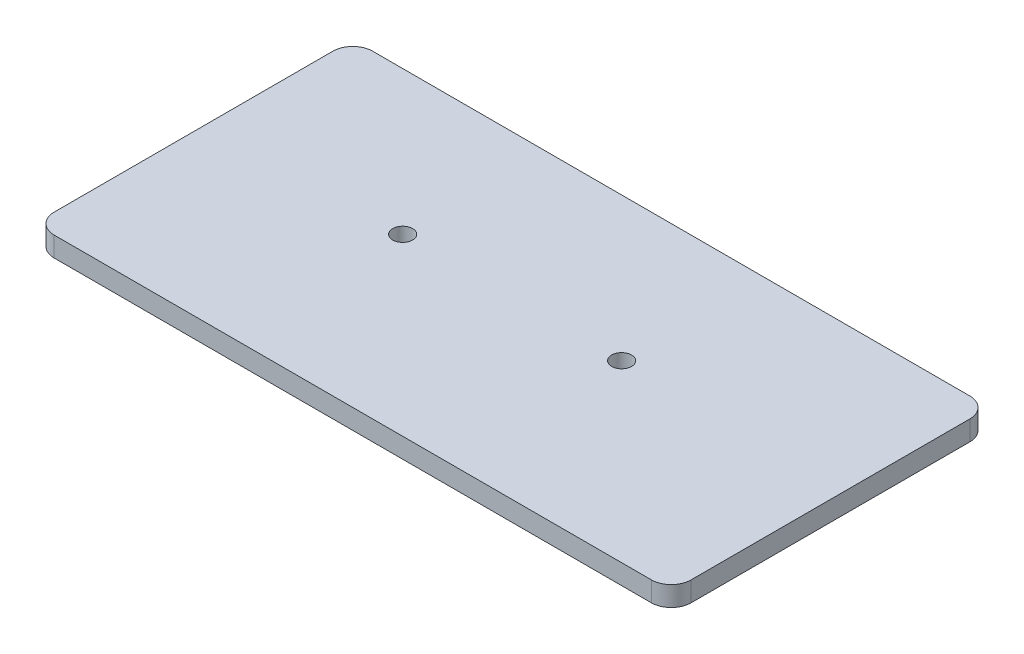
SolidWorks part; units mm, degrees
ref_plane "Front Plane" through (0, 0, 0) normal (0, 0, 1) x (1, 0, 0)
ref_plane "Top Plane" through (0, 0, 0) normal (0, 1, 0) x (1, 0, 0)
ref_plane "Right Plane" through (0, 0, 0) normal (1, 0, 0) x (0, 0, -1)
sketch "Sketch1" plane through (0, 0, 0) normal (0, 1, 0) x (1, 0, 0)
  line L1 (0, 0) -> (203.2, 0)
  line L2 (0, 0) -> (0, 101.6)
  line L3 (0, 101.6) -> (203.2, 101.6)
  line L4 (203.2, 0) -> (203.2, 101.6)
  dimension "D1" = 101.6
  dimension "D2" = 203.2
extrude "Boss-Extrude1" add sketch "Sketch1" along normal blind 6.35
hole_wizard "1/4 (0.25) Diameter Hole1" positions "Sketch2" profile "Sketch3" hole size "1/4" standard "ANSI Inch" end condition through all
sketch "Sketch2" plane through (0, 6.35, 0) normal (0, 1, 0) x (1, 0, 0)
  point P0 (61.7268, 55.7935)
  point P2 (131.5768, 55.7935)
  dimension "D1" = 69.85
sketch "Sketch3" plane through (61.7268, 6.35, -55.7935) normal (1, 0, 0) x (0, 0, 1)
  line L0 (0, 0) -> (0, 6.35)
  line L1 (0, 6.35) -> (3.175, 6.35)
  line L2 (3.175, 6.35) -> (3.175, 0)
  line L5 (3.175, 0) -> (0, 0)
  line L11 (0, -6.35) -> (0, 107.95) construction
  dimension "Thru Hole Dia." = 6.35
  dimension "Thru Hole Depth" = 6.35
fillet "Fillet1" radius 6.35 4 edges at (203.2, 3.175, 0) (203.2, 3.175, -101.6) (0, 3.175, -101.6) (0, 3.175, 0)
